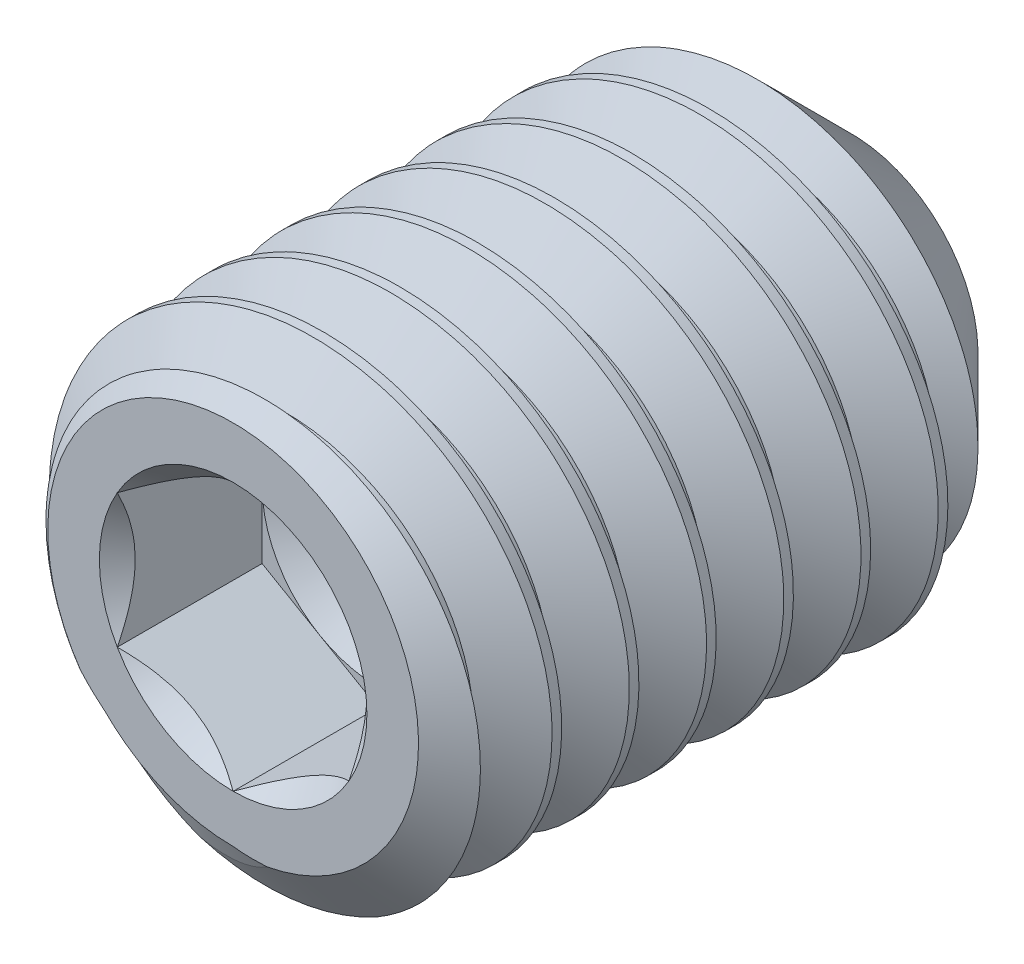
SolidWorks part; units mm, degrees
material "Nylon 6/10"
ref_plane "Front" through (0, 0, 0) normal (0, 0, 1) x (1, 0, 0)
ref_plane "Top" through (0, 0, 0) normal (0, 1, 0) x (1, 0, 0)
ref_plane "Right" through (0, 0, 0) normal (1, 0, 0) x (0, 0, -1)
sketch "Sketch22" plane through (0, 0, 0) normal (1, 0, 0) x (0, 0, -1)
  line L0 (-5.566, 0) -> (-5.566, 3.81)
  line L1 (-5.566, 3.81) -> (-4.899, 4.7625)
  line L2 (-4.899, 4.7625) -> (4.9812, 4.7625)
  line L3 (4.9812, 4.7625) -> (7.134, 2.6097)
  line L4 (7.134, 2.6097) -> (5.566, 0) construction
  line L5 (5.566, 0) -> (-5.566, 0)
  line L6 (5.566, 0) -> (7.134, 0) construction
  line L7 (7.134, 0) -> (7.134, 2.6097) construction
  line L8 (7.134, -2.6097) -> (5.566, 0) construction
  line L9 (-4.899, -4.7625) -> (4.9812, -4.7625) construction
  line L10 (7.134, 2.6097) -> (7.134, 0)
  line L11 (7.134, 0) -> (5.566, 0)
  dimension "Dia" = 9.525
  dimension "Length" = 12.7
  dimension "D3" = 35
  dimension "D5" = 118
  dimension "D6" = 45
  dimension "D7" = 7.62
revolve "Revolve1" add sketch "Sketch22" angle 360 about L6
ref_plane "Plane1" through (0, 0, -7.134) normal (0, 0, 1) x (1, 0, 0)
sketch "Sketch27" plane through (0, 0, -7.134) normal (0, 0, 1) x (1, 0, 0)
  circle A0 centre (0, 0) radius 4.7625 construction
  circle A1 centre (0, 0) radius 4.7625
curve "Helix/Spiral1" pitch 1.5875 height 14.2875 radius 4.7625 centre (0, 0, -7.134) axis (0, 0, 1) start towards (0, 1, 0)
sketch "Sketch28" plane through (0, 0, 0) normal (1, 0, 0) x (0, 0, -1)
  line L0 (7.134, 4.7625) -> (8.5231, 4.7625)
  line L1 (8.5231, 4.7625) -> (7.9278, 3.7314)
  line L2 (7.9278, 3.7314) -> (7.7293, 3.7314)
  line L3 (7.7293, 3.7314) -> (7.134, 4.7625)
  line L4 (7.4317, 4.2469) -> (8.2254, 4.2469) construction
  line L6 (-4.899, 4.7625) -> (4.9812, 4.7625) construction
  line L7 (7.134, 4.3586) -> (7.134, -4.3586) construction
  dimension "D1" = 0.1984
  dimension "D3" = 60
  dimension "D2" = 0.7937
sweep "Cut-Sweep2" cut profiles "Sketch28" path "Helix/Spiral1" align with end faces yes
sketch "Sketch23" plane through (0, 0, 5.566) normal (0, 0, 1) x (1, 0, 0)
  line L1 (0, 2.7496) -> (-2.3813, 1.3748)
  line L2 (-2.3813, 1.3748) -> (-2.3813, -1.3748)
  line L3 (-2.3813, -1.3748) -> (0, -2.7496)
  line L4 (0, -2.7496) -> (2.3812, -1.3748)
  line L5 (2.3812, -1.3748) -> (2.3812, 1.3748)
  line L6 (2.3812, 1.3748) -> (0, 2.7496)
  circle A0 centre (0, 0) radius 2.3813 construction
  dimension "Hex" = 4.7625
extrude "Cut-Extrude10" cut sketch "Sketch23" against normal blind 2.9766
sketch "Sketch24" plane through (0, 0, 5.566) normal (0, 0, 1) x (1, 0, 0)
  circle A0 centre (0, 0) radius 2.7496
extrude "Cut-Extrude11" cut sketch "Sketch24" against normal through all draft 45
sketch "Sketch26" plane through (0, 0, 2.5894) normal (0, 0, 1) x (1, 0, 0)
  circle A0 centre (0, 0) radius 2.3813 construction
  circle A1 centre (0, 0) radius 2.3813
extrude "Cut-Extrude12" cut sketch "Sketch26" against normal through all draft 60
sketch "Sketch30" plane through (0, 0, 0) normal (1, 0, 0) x (0, 0, -1)
  line L0 (-4.899, 4.7625) -> (4.9812, 4.7625) construction
  line L1 (-5.566, 0) -> (-5.566, 3.81) construction
  line L2 (7.134, 0) -> (7.134, 2.6097) construction
  line L3 (-4.899, -4.7625) -> (4.9812, -4.7625) construction
  point P0 (-5.566, 4.7625)
  point P1 (7.134, 4.7625)
  point P2 (7.134, -4.7625)
  point P11 (1.5778, -4.7625)
  dimension "D1" = 5.5562
sketch "Sketch31" plane through (0, 0, 0) normal (1, 0, 0) x (0, 0, -1)
  line L2 (5.566, 0) -> (7.134, -2.6097)
  line L3 (7.134, 2.6097) -> (5.566, 0)
equation "\"D7@Sketch22\"=\"Dia@Sketch22\"*.8"
equation "\"D1@Sketch28\" = \"D4@Helix/Spiral1\" * .125"
equation "\"D3@Helix/Spiral1\" = \"Length@Sketch22\" + \"D4@Helix/Spiral1\""
equation "\"D1@Sketch30\" = \"D4@Helix/Spiral1\" * 3.5"
equation "\"hex Depth@Cut-Extrude10\" = \"Hex@Sketch23\" * .625"
equation "\"D2@Sketch28\" = \"D4@Helix/Spiral1\" * .5"
